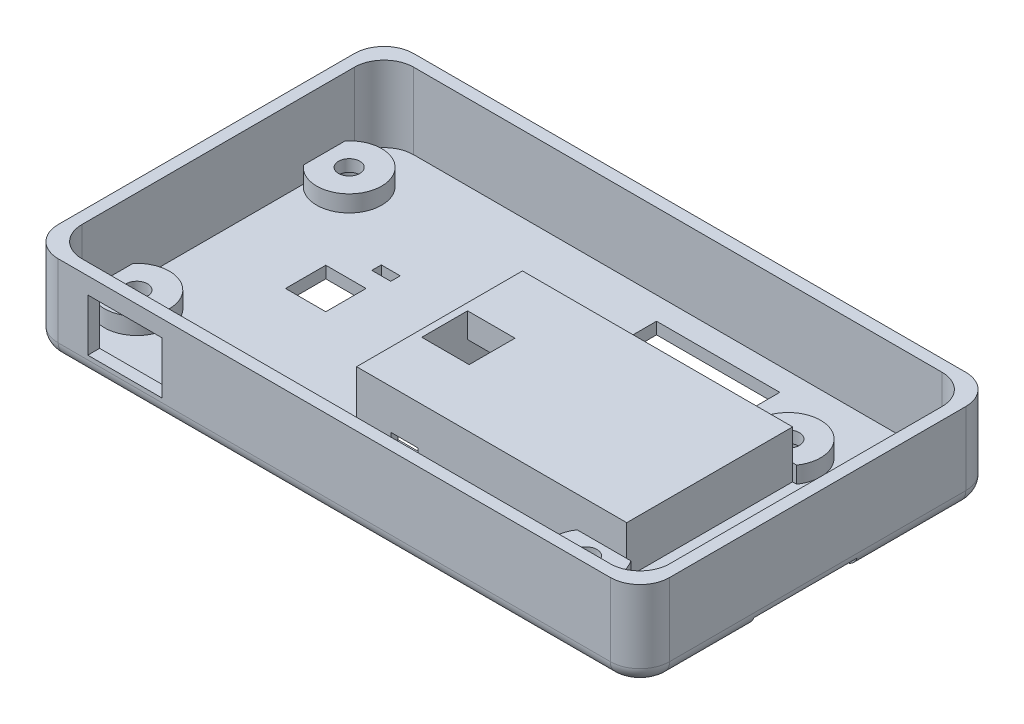
SolidWorks part; units mm, degrees
material "ABS"
ref_plane "Спереди" through (0, 0, 0) normal (0, 0, 1) x (1, 0, 0)
ref_plane "Сверху" through (0, 0, 0) normal (0, 1, 0) x (1, 0, 0)
ref_plane "Справа" through (0, 0, 0) normal (1, 0, 0) x (0, 0, -1)
sketch "Эскиз1" plane through (0, 0, 0) normal (0, 1, 0) x (1, 0, 0)
  line L11 (61.92, -36) -> (-61.92, -36)
  line L12 (61.92, -36) -> (61.92, 36)
  line L13 (61.92, 36) -> (-61.92, 36)
  line L14 (-61.92, -36) -> (-61.92, 36)
  point P0 (0, 0)
extrude "Бобышка-Вытянуть1" add sketch "Эскиз1" along normal blind 17.76
sketch "Эскиз8" plane through (0, 17.76, 0) normal (0, 1, 0) x (1, 0, 0)
  line L7 (-59.52, 33.6) -> (59.52, 33.6)
  line L8 (-59.52, 33.6) -> (-59.52, -33.6)
  line L9 (-59.52, -33.6) -> (59.52, -33.6)
  line L10 (59.52, 33.6) -> (59.52, -33.6)
extrude "Вырез-Вытянуть5" cut sketch "Эскиз8" against normal blind 15.36
sketch "Эскиз10" plane through (0, 2.4, 0) normal (0, 1, 0) x (1, 0, 0)
  line L0 (-61.92, 0) -> (96.256, 0) construction
  line L1 (-61.92, 36) -> (-61.92, -36) construction
  line L3 (42.24, 14.6) -> (42.24, -19)
  line L4 (42.24, -19) -> (-12.48, -19)
  line L5 (-12.48, 14.6) -> (-12.48, -19)
  line L9 (42.24, 14.6) -> (-12.48, 14.6)
sketch "Эскиз11" plane through (0, 0, 33.6) normal (0, 0, 1) x (1, 0, 0)
  line L3 (-49.92, 3.84) -> (-34.92, 3.84)
  line L4 (-49.92, 3.84) -> (-49.92, 14.4)
  line L5 (-49.92, 14.4) -> (-34.92, 14.4)
  line L6 (-34.92, 3.84) -> (-34.92, 14.4)
extrude "Бобышка-Вытянуть2" add sketch "Эскиз10" along normal blind 9.64
extrude "Вырез-Вытянуть7" cut sketch "Эскиз11" along normal blind 5
sketch "Эскиз12" plane through (0, 0, 0) normal (0, -1, 0) x (1, 0, 0)
  line L0 (-59.52, 0) -> (69.6149, 0) construction
  line L2 (40.32, -12.68) -> (40.32, 17.56)
  line L3 (-11.04, 17.56) -> (40.32, 17.56)
  line L4 (-11.04, -12.68) -> (-11.04, 17.56)
  line L9 (-11.04, -12.68) -> (40.32, -12.68)
  point P3 (57.4685, 0)
extrude "Вырез-Вытянуть8" cut sketch "Эскиз12" against normal blind 7
sketch "Эскиз13" plane through (0, 0, 0) normal (0, -1, 0) x (1, 0, 0)
  line L1 (-59.52, 0) -> (-76.8441, 0) construction
  line L8 (37.32, 12.76) -> (61.92, 12.76)
  line L9 (37.32, -8.2) -> (37.32, 12.76)
  line L10 (61.92, -8.2) -> (61.92, 12.76)
  line L11 (61.92, -8.2) -> (37.32, -8.2)
  point P12 (0, 0)
extrude "Вырез-Вытянуть9" cut sketch "Эскиз13" against normal blind 2
sketch "Эскиз21" plane through (0, 7, 0) normal (0, -1, 0) x (1, 0, 0)
  line L1 (0, 0) -> (59.52, 0) construction
  line L8 (-1.44, 7.24) -> (-1.44, -2.04)
  line L9 (-11.04, 7.24) -> (-1.44, 7.24)
  line L10 (-11.04, -2.04) -> (-1.44, -2.04)
  line L11 (-11.04, 2.44) -> (-11.04, 7.24)
  line L12 (-11.04, 2.44) -> (-11.04, -2.04)
extrude "Вырез-Вытянуть16" cut sketch "Эскиз21" against normal through all
sketch "Эскиз14" plane through (0, 0, 0) normal (0, -1, 0) x (1, 0, 0)
  circle A1 centre (-54.48, -21.5) radius 2.16
  circle A3 centre (37.64, -18.3) radius 2.26
  circle A4 centre (37.64, 22.7) radius 2.26
  circle A6 centre (-54.48, 21.5) radius 2.16
  point P4 (0, 0)
sketch "Эскиз22" plane through (0, 0, 0) normal (0, -1, 0) x (1, 0, 0)
  line L0 (-59.52, 0) -> (59.52, 0) construction
  circle A0 centre (37.64, -18.3) radius 3.71
  circle A1 centre (37.64, 22.7) radius 3.71
  circle A4 centre (-54.48, 21.5) radius 3.12
  circle A5 centre (-54.48, -21.5) radius 3.12
fillet "Скругление1" radius 6 4 edges at (-61.92, 8.88, 36) (-61.92, 8.88, -36) (61.92, 8.88, -36) (61.92, 8.88, 36)
fillet "Скругление3" radius 3 8 edges at (60.1626, 0, -34.2426) (0, 0, -36) (-60.1626, 0, -34.2426) (-61.92, 0, 0) (-60.1626, 0, 34.2426) (61.92, 0, 21.38) (60.1626, 0, 34.2426) (0, 0, 36)
fillet "Скругление5" radius 6 4 edges at (-59.52, 10.08, 33.6) (-59.52, 10.08, -33.6) (59.52, 10.08, 33.6) (59.52, 10.08, -33.6)
sketch "Эскиз19" plane through (0, 0, 17.56) normal (0, 0, -1) x (-1, 0, 0)
  line L4 (5.5, 2) -> (0, 2)
  line L5 (5.5, 2) -> (5.5, 4)
  line L6 (5.5, 4) -> (0, 4)
  line L7 (0, 2) -> (0, 4)
extrude "Вырез-Вытянуть14" cut sketch "Эскиз19" against normal blind 3.84
sketch "Эскиз20" plane through (0, 0, -12.68) normal (0, 0, 1) x (1, 0, 0)
  line L4 (-5.5, 2) -> (0, 2)
  line L5 (-5.5, 2) -> (-5.5, 4)
  line L6 (-5.5, 4) -> (0, 4)
  line L7 (0, 2) -> (0, 4)
extrude "Вырез-Вытянуть15" cut sketch "Эскиз20" against normal blind 3.84
sketch "Эскиз23" plane through (0, 2.4, 0) normal (0, 1, 0) x (1, 0, 0)
  line L1 (-59.52, 25.7302) -> (-59.52, 17.2698)
  line L3 (-59.52, 27.6) -> (-59.52, -27.6) construction
  line L4 (-59.52, -25.7302) -> (-59.52, -17.2698)
  arc A0 (-59.52, 17.2698) -> (-59.52, 25.7302) centre (-54.48, 21.5) ccw
  arc A2 (-59.52, -25.7302) -> (-59.52, -17.2698) centre (-54.48, -21.5) ccw
sketch "Эскиз24" plane through (0, 2.4, 0) normal (0, 1, 0) x (1, 0, 0)
  line L3 (-59.52, 0) -> (71.623, 0) construction
  line L6 (32.1988, -19) -> (43.0812, -19)
  line L7 (32.1988, 14.6) -> (43.0759, 14.5923)
  arc A2 (32.1988, -19) -> (43.0812, -19) centre (37.64, -22.7) ccw
  arc A3 (32.1988, 14.6) -> (43.0759, 14.5923) centre (37.64, 18.3) cw
extrude "Бобышка-Вытянуть3" add sketch "Эскиз24" along normal blind 3.36
extrude "Бобышка-Вытянуть4" add sketch "Эскиз23" along normal blind 3.36
sketch "Эскиз25" plane through (0, 0, 0) normal (0, 1, 0) x (1, 0, 0)
  line L0 (-59.52, 0) -> (57.2984, 0) construction
  circle A0 centre (-54.48, -21.5) radius 2.16
  circle A1 centre (-54.48, 21.5) radius 2.16
  circle A4 centre (37.64, 18.3) radius 2.26
  circle A5 centre (37.64, -22.7) radius 2.26
extrude "Вырез-Вытянуть17" cut sketch "Эскиз25" along normal through all
extrude "Вырез-Вытянуть18" cut sketch "Эскиз22" against normal blind 3.36
sketch "Эскиз26" plane through (0, 0, 0) normal (0, -1, 0) x (1, 0, 0)
  line L0 (-59.52, 0) -> (71.8908, 0) construction
  line L2 (0.2816, -17.96) -> (0.2816, -29)
  line L7 (25.2416, -29) -> (0.2816, -29)
  line L8 (-33.64, -11) -> (-37.48, -11)
  line L9 (-34.88, 2.84) -> (-43.04, 2.84)
  line L10 (-34.88, 2.84) -> (-34.88, -5.32)
  line L11 (-34.88, -5.32) -> (-43.04, -5.32)
  line L12 (-43.04, 2.84) -> (-43.04, -5.32)
  line L13 (-37.48, -11) -> (-37.48, -9.08)
  line L14 (-37.48, -9.08) -> (-33.64, -9.08)
  line L15 (-33.64, -9.08) -> (-33.64, -11)
  line L16 (25.2416, -17.96) -> (25.2416, -29)
  line L17 (25.2416, -17.96) -> (0.2816, -17.96)
extrude "Вырез-Вытянуть19" cut sketch "Эскиз26" against normal through all
